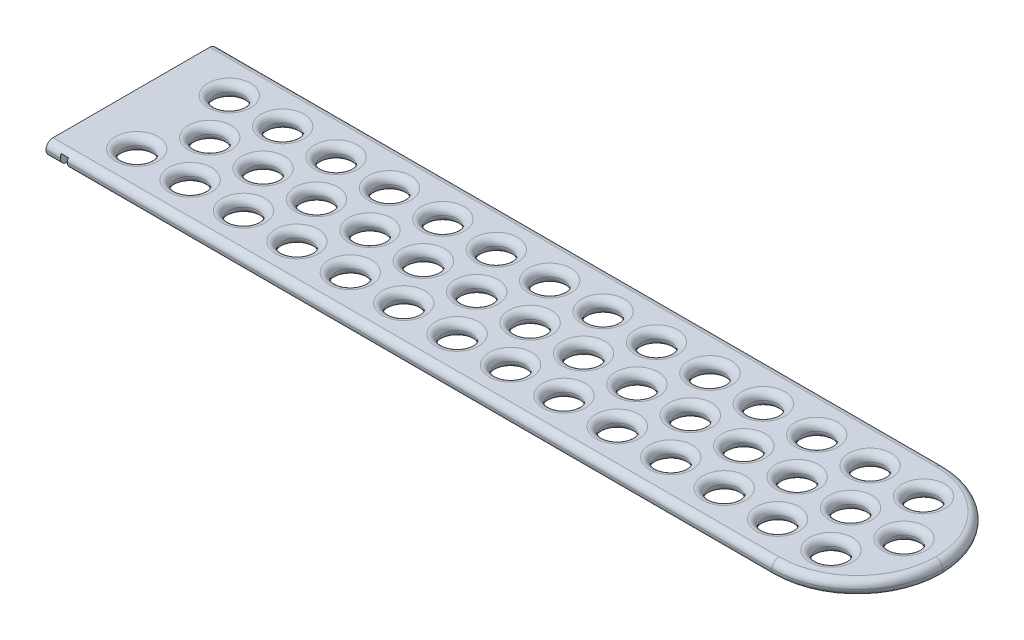
SolidWorks part; units mm, degrees
ref_plane "Front Plane" through (0, 0, 0) normal (0, 0, 1) x (1, 0, 0)
ref_plane "Top Plane" through (0, 0, 0) normal (0, 1, 0) x (1, 0, 0)
ref_plane "Right Plane" through (0, 0, 0) normal (1, 0, 0) x (0, 0, -1)
sketch "Sketch1" plane through (0, 0, 0) normal (0, 1, 0) x (1, 0, 0)
  line L1 (22.7264, 12) -> (137.7264, 12)
  line L2 (22.7264, 12) -> (22.7264, -12)
  line L3 (22.7264, -12) -> (137.7264, -12)
  line L4 (137.7264, 12) -> (137.7264, -12)
  dimension "D1" = 24
  dimension "D2" = 115
extrude "Boss-Extrude1" add sketch "Sketch1" along normal blind 2
fillet "Fillet4" radius 12 2 edges at (137.7264, 1, 12) (137.7264, 1, -12)
sketch "Sketch4" plane through (0, 2, 0) normal (0, 1, 0) x (1, 0, 0)
  line L0 (30.9736, 6.5) -> (34.7264, 0) construction
  line L1 (34.7264, 0) -> (30.9736, -6.5) construction
  line L2 (22.7264, 12) -> (22.7264, -12) construction
  circle A0 centre (30.9736, 6.5) radius 2
  circle A1 centre (34.7264, 0) radius 2
  circle A2 centre (30.9736, -6.5) radius 2
  circle A3 centre (42.2292, 0) radius 2
  circle A4 centre (38.4764, 6.5) radius 2
  circle A5 centre (38.4764, -6.5) radius 2
  circle A6 centre (49.732, 0) radius 2
  circle A7 centre (45.9792, 6.5) radius 2
  circle A8 centre (45.9792, -6.5) radius 2
  circle A9 centre (57.2347, 0) radius 2
  circle A10 centre (53.482, 6.5) radius 2
  circle A11 centre (53.482, -6.5) radius 2
  circle A12 centre (64.7375, 0) radius 2
  circle A13 centre (60.9847, 6.5) radius 2
  circle A14 centre (60.9847, -6.5) radius 2
  circle A15 centre (72.2403, 0) radius 2
  circle A16 centre (68.4875, 6.5) radius 2
  circle A17 centre (68.4875, -6.5) radius 2
  circle A18 centre (79.7431, 0) radius 2
  circle A19 centre (75.9903, 6.5) radius 2
  circle A20 centre (75.9903, -6.5) radius 2
  circle A21 centre (87.2459, 0) radius 2
  circle A22 centre (83.4931, 6.5) radius 2
  circle A23 centre (83.4931, -6.5) radius 2
  circle A24 centre (94.7486, 0) radius 2
  circle A25 centre (90.9959, 6.5) radius 2
  circle A26 centre (90.9959, -6.5) radius 2
  circle A27 centre (102.2514, 0) radius 2
  circle A28 centre (98.4986, 6.5) radius 2
  circle A29 centre (98.4986, -6.5) radius 2
  circle A30 centre (109.7542, 0) radius 2
  circle A31 centre (106.0014, 6.5) radius 2
  circle A32 centre (106.0014, -6.5) radius 2
  circle A33 centre (117.257, 0) radius 2
  circle A34 centre (113.5042, 6.5) radius 2
  circle A35 centre (113.5042, -6.5) radius 2
  circle A36 centre (124.7597, 0) radius 2
  circle A37 centre (121.007, 6.5) radius 2
  circle A38 centre (121.007, -6.5) radius 2
  circle A39 centre (132.2625, 0) radius 2
  circle A40 centre (128.5097, 6.5) radius 2
  circle A41 centre (128.5097, -6.5) radius 2
  point P11 (22.7264, 0)
  dimension "D1" = 4
  dimension "D2" = 120
  dimension "D3" = 12
  dimension "D5" = 3.75
  dimension "D6" = 13
  dimension "D4" = 14
extrude "Cut-Extrude2" cut sketch "Sketch4" against normal through all
fillet "Fillet3" radius 1 94 edges at (74.2264, 0, 12) (74.2264, 0, -12) (30.9736, 0, -4.5) (113.5042, 0, 8.5) (117.257, 0, 2) (113.5042, 0, -4.5) (60.9847, 0, -4.5) (53.482, 0, 8.5) (57.2347, 0, 2) (53.482, 0, -4.5) (72.2403, 0, 2) (68.4875, 0, -4.5) (60.9847, 0, 8.5) (64.7375, 0, 2) (42.2292, 0, 2) (38.4764, 0, -4.5) (30.9736, 0, 8.5) (34.7264, 0, 2) (45.9792, 0, 8.5) (49.732, 0, 2) (45.9792, 0, -4.5) (38.4764, 0, 8.5) (102.2514, 0, 2) (98.4986, 0, -4.5) (90.9959, 0, 8.5) (94.7486, 0, 2) (106.0014, 0, 8.5) (109.7542, 0, 2) (106.0014, 0, -4.5) (98.4986, 0, 8.5) (75.9903, 0, 8.5) (79.7431, 0, 2) (75.9903, 0, -4.5) (68.4875, 0, 8.5) (90.9959, 0, -4.5) (83.4931, 0, 8.5) (87.2459, 0, 2) (83.4931, 0, -4.5) (74.2264, 2, 12) (74.2264, 2, -12) (30.9736, 2, -4.5) (113.5042, 2, 8.5) (117.257, 2, 2) (113.5042, 2, -4.5) (60.9847, 2, -4.5) (53.482, 2, 8.5) (57.2347, 2, 2) (53.482, 2, -4.5) (72.2403, 2, 2) (68.4875, 2, -4.5) (60.9847, 2, 8.5) (64.7375, 2, 2) (42.2292, 2, 2) (38.4764, 2, -4.5) (30.9736, 2, 8.5) (34.7264, 2, 2) (45.9792, 2, 8.5) (49.732, 2, 2) (45.9792, 2, -4.5) (38.4764, 2, 8.5) (102.2514, 2, 2) (98.4986, 2, -4.5) (90.9959, 2, 8.5) (94.7486, 2, 2) (106.0014, 2, 8.5) (109.7542, 2, 2) (106.0014, 2, -4.5) (98.4986, 2, 8.5) (75.9903, 2, 8.5) (79.7431, 2, 2) (75.9903, 2, -4.5) (68.4875, 2, 8.5) (90.9959, 2, -4.5) (83.4931, 2, 8.5) (87.2459, 2, 2) (83.4931, 2, -4.5) (128.5097, 0, -4.5) (128.5097, 2, -4.5) (22.7264, 0, 0) (22.7264, 2, 0) (132.2625, 0, 2) (121.007, 0, 8.5) (128.5097, 0, 8.5) (121.007, 0, -4.5) (124.7597, 0, 2) (132.2625, 2, 2) (121.007, 2, 8.5) (128.5097, 2, 8.5) (121.007, 2, -4.5) (124.7597, 2, 2) (134.2117, 0, 8.4853) (134.2117, 0, -8.4853) (134.2117, 2, -8.4853) (134.2117, 2, 8.4853)
sketch "Sketch11" plane through (0, 2, 0) normal (0, 1, 0) x (1, 0, 0)
  line L0 (125.7264, -12) -> (22.7264, -12) construction
  line L1 (22.7264, 12) -> (23.7264, 12)
  line L2 (22.7264, 12) -> (22.7264, -12)
  line L3 (22.7264, -12) -> (23.7264, -12)
  line L4 (23.7264, 12) -> (23.7264, -12)
  line L5 (23.7264, 11) -> (23.7264, -11) construction
extrude "Cut-Extrude6" cut sketch "Sketch11" against normal through all both and the other way through all
sketch "Sketch12" plane through (0, 0, 0) normal (0, -1, 0) x (1, 0, 0)
  line L0 (125.7264, 12) -> (23.7264, 12) construction
  line L1 (25.7264, 12) -> (26.7264, 12)
  line L2 (25.7264, 12) -> (25.7264, -12)
  line L3 (25.7264, -12) -> (26.7264, -12)
  line L4 (26.7264, 12) -> (26.7264, -12)
  line L5 (23.7264, -12) -> (125.7264, -12) construction
  line L6 (23.7264, 11) -> (23.7264, -11) construction
  dimension "D1" = 2
  dimension "D2" = 1
extrude "Cut-Extrude7" cut sketch "Sketch12" against normal blind 1.5
